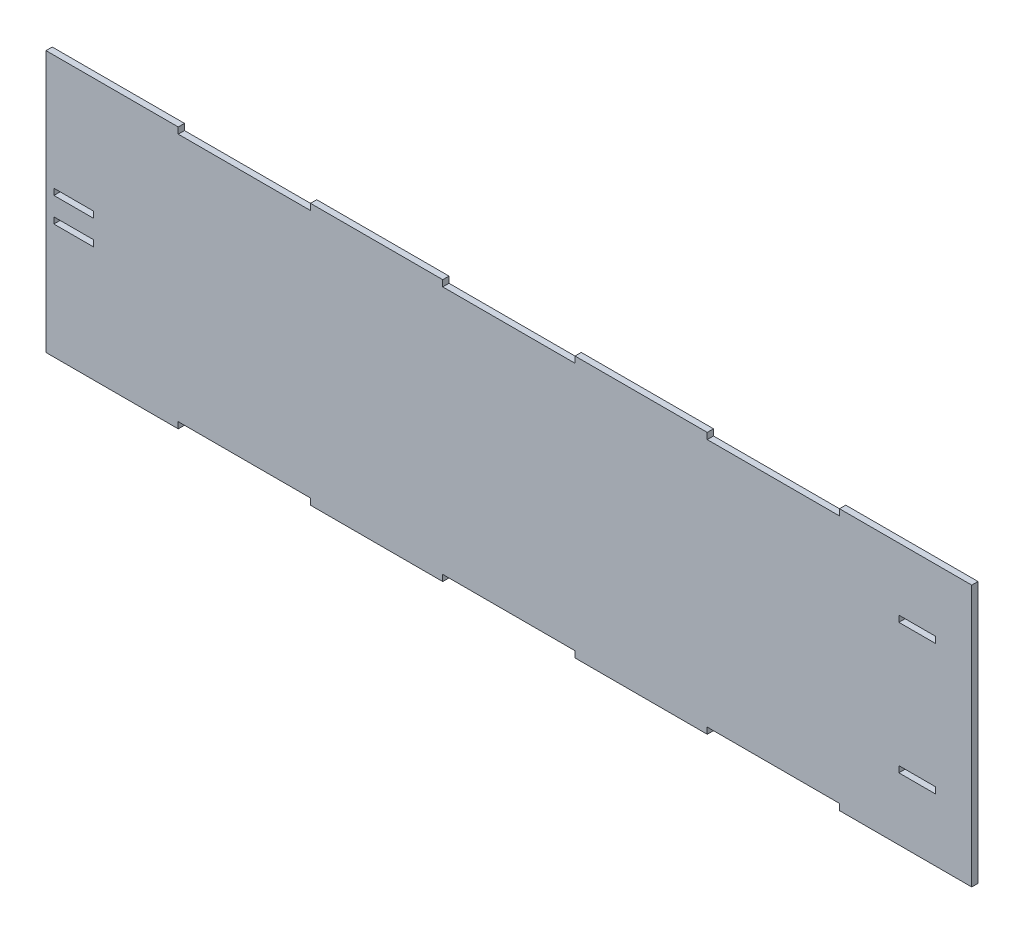
SolidWorks part; units mm, degrees
ref_plane "Front Plane" through (0, 0, 0) normal (0, 0, 1) x (1, 0, 0)
ref_plane "Top Plane" through (0, 0, 0) normal (0, 1, 0) x (1, 0, 0)
ref_plane "Right Plane" through (0, 0, 0) normal (1, 0, 0) x (0, 0, -1)
sketch "Sketch1" plane through (0, 0, 0) normal (0, 0, 1) x (1, 0, 0)
  line L0 (0, 132.75) -> (67.1429, 132.75)
  line L1 (0, 0) -> (470, 0) construction
  line L2 (0, 0) -> (0, 132.75)
  line L4 (470, 0) -> (470, 132.75)
  line L5 (67.1429, 132.75) -> (67.1429, 129.575)
  line L6 (67.1429, 129.575) -> (134.2857, 129.575)
  line L7 (134.2857, 129.575) -> (134.2857, 132.75)
  line L8 (134.2857, 132.75) -> (201.4286, 132.75)
  line L9 (201.4286, 132.75) -> (201.4286, 129.575)
  line L10 (201.4286, 129.575) -> (268.5714, 129.575)
  line L11 (268.5714, 129.575) -> (268.5714, 132.75)
  line L12 (268.5714, 132.75) -> (335.7143, 132.75)
  line L13 (335.7143, 132.75) -> (335.7143, 129.575)
  line L14 (335.7143, 129.575) -> (402.8571, 129.575)
  line L15 (402.8571, 129.575) -> (402.8571, 132.75)
  line L16 (402.8571, 132.75) -> (470, 132.75)
  line L17 (0, 66.375) -> (470, 66.375) construction
  line L18 (402.8571, 0) -> (470, 0)
  line L19 (402.8571, 3.175) -> (402.8571, 0)
  line L20 (335.7143, 3.175) -> (402.8571, 3.175)
  line L21 (335.7143, 0) -> (335.7143, 3.175)
  line L22 (268.5714, 0) -> (335.7143, 0)
  line L23 (268.5714, 3.175) -> (268.5714, 0)
  line L24 (201.4286, 3.175) -> (268.5714, 3.175)
  line L25 (201.4286, 0) -> (201.4286, 3.175)
  line L26 (134.2857, 0) -> (201.4286, 0)
  line L27 (134.2857, 3.175) -> (134.2857, 0)
  line L28 (67.1429, 3.175) -> (134.2857, 3.175)
  line L29 (67.1429, 0) -> (67.1429, 3.175)
  line L30 (0, 0) -> (67.1429, 0)
  line L31 (4, 61.675) -> (4, 66.375) construction
  line L32 (4, 61.675) -> (24, 61.675)
  line L33 (4, 61.675) -> (4, 58.5)
  line L34 (4, 58.5) -> (24, 58.5)
  line L35 (24, 61.675) -> (24, 58.5)
  line L36 (4, 71.075) -> (24, 71.075)
  line L37 (4, 71.075) -> (4, 74.25)
  line L38 (4, 74.25) -> (24, 74.25)
  line L39 (24, 71.075) -> (24, 74.25)
  line L40 (451.5, 66.375) -> (451.5, 97.875) construction
  line L41 (451.5, 34.875) -> (433, 34.875)
  line L42 (451.5, 97.875) -> (433, 97.875)
  line L43 (451.5, 97.875) -> (451.5, 101.05)
  line L44 (451.5, 101.05) -> (433, 101.05)
  line L45 (433, 97.875) -> (433, 101.05)
  line L46 (451.5, 34.875) -> (451.5, 31.7)
  line L47 (451.5, 31.7) -> (433, 31.7)
  line L48 (433, 34.875) -> (433, 31.7)
  dimension "D1" = 470
  dimension "D2" = 132.75
  dimension "D3" = 3.175
  dimension "D4" = 9.4
  dimension "D5" = 3.175
  dimension "D6" = 20
  dimension "D7" = 4.7
  dimension "D8" = 4
  dimension "D9" = 31.5
  dimension "D10" = 18.5
  dimension "D11" = 18.5
  dimension "D12" = 3.175
extrude "Boss-Extrude1" add sketch "Sketch1" along normal blind 3.175
